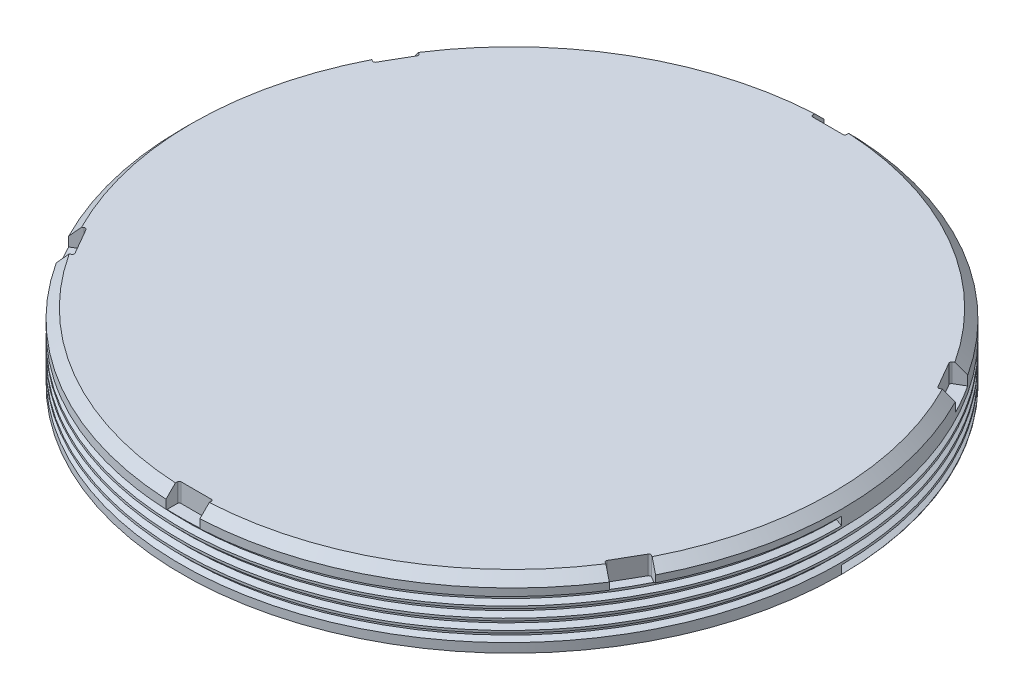
SolidWorks part; units mm, degrees
ref_plane "Front Plane" through (0, 0, 0) normal (0, 0, 1) x (1, 0, 0)
ref_plane "Top Plane" through (0, 0, 0) normal (0, 1, 0) x (1, 0, 0)
ref_plane "Right Plane" through (0, 0, 0) normal (1, 0, 0) x (0, 0, -1)
sketch "Sketch1" plane through (0, 0, 0) normal (0, 1, 0) x (1, 0, 0)
  circle A0 centre (0, 0) radius 17.5
  dimension "D1" = 35
extrude "Boss-Extrude1" add sketch "Sketch1" along normal blind 3.5
chamfer "Chamfer1" distance 0.5 angle 45 1 edges at (0, 3.5, 17.5)
sketch "Sketch3" plane through (0, 3.5, 0) normal (0, 1, 0) x (1, 0, 0)
  line L0 (14.1636, 9.2166) -> (14.7006, 9.5266)
  line L1 (14.127, 9.08) -> (14.927, 7.6944)
  line L2 (-0.8, 16.7744) -> (0.8, 16.7744)
  line L3 (0.9, 16.8744) -> (0.9, 17.4944)
  line L4 (-0.9, 16.8744) -> (-0.9, 17.4944)
  line L5 (15.0636, 7.6578) -> (15.6006, 7.9678)
  line L6 (15.0636, -7.6578) -> (15.6006, -7.9678)
  line L7 (14.927, -7.6944) -> (14.127, -9.08)
  line L8 (14.1636, -9.2166) -> (14.7006, -9.5266)
  line L9 (0.9, -16.8744) -> (0.9, -17.4944)
  line L10 (0.8, -16.7744) -> (-0.8, -16.7744)
  line L11 (-0.9, -16.8744) -> (-0.9, -17.4944)
  line L12 (-14.1636, -9.2166) -> (-14.7006, -9.5266)
  line L13 (-14.127, -9.08) -> (-14.927, -7.6944)
  line L14 (-15.0636, -7.6578) -> (-15.6006, -7.9678)
  line L15 (-15.0636, 7.6578) -> (-15.6006, 7.9678)
  line L16 (-14.927, 7.6944) -> (-14.127, 9.08)
  line L17 (-14.1636, 9.2166) -> (-14.7006, 9.5266)
  arc A0 (-14.7006, 9.5266) -> (-15.6006, 7.9678) centre (0, 0) ccw
  arc A1 (0.9, 16.8744) -> (0.8, 16.7744) centre (0.8, 16.8744) cw
  arc A2 (-0.9, 16.8744) -> (-0.8, 16.7744) centre (-0.8, 16.8744) ccw
  arc A3 (14.1636, 9.2166) -> (14.127, 9.08) centre (14.2136, 9.13) ccw
  arc A4 (15.0636, 7.6578) -> (14.927, 7.6944) centre (15.0136, 7.7444) cw
  arc A5 (15.0636, -7.6578) -> (14.927, -7.6944) centre (15.0136, -7.7444) ccw
  arc A6 (14.1636, -9.2166) -> (14.127, -9.08) centre (14.2136, -9.13) cw
  arc A7 (0.9, -16.8744) -> (0.8, -16.7744) centre (0.8, -16.8744) ccw
  arc A8 (-0.9, -16.8744) -> (-0.8, -16.7744) centre (-0.8, -16.8744) cw
  arc A9 (-14.1636, -9.2166) -> (-14.127, -9.08) centre (-14.2136, -9.13) ccw
  arc A10 (-15.0636, -7.6578) -> (-14.927, -7.6944) centre (-15.0136, -7.7444) cw
  arc A11 (-15.0636, 7.6578) -> (-14.927, 7.6944) centre (-15.0136, 7.7444) ccw
  arc A12 (-14.1636, 9.2166) -> (-14.127, 9.08) centre (-14.2136, 9.13) cw
  arc A13 (0.9, 17.4944) -> (-0.9, 17.4944) centre (0, 0) ccw
  arc A14 (15.6006, 7.9678) -> (14.7006, 9.5266) centre (0, 0) ccw
  arc A15 (-15.6006, -7.9678) -> (-14.7006, -9.5266) centre (0, 0) ccw
  arc A16 (-0.9, -17.4944) -> (0.9, -17.4944) centre (0, 0) ccw
  arc A17 (14.7006, -9.5266) -> (15.6006, -7.9678) centre (0, 0) ccw
  point P54 (0, 0)
  dimension "D1" = 6
  dimension "D2" = 0.62
extrude "Cut-Extrude1" cut sketch "Sketch3" against normal blind 1
sketch "Sketch4" plane through (0, 0, 0) normal (0, -1, 0) x (-1, 0, 0)
  circle A0 centre (0, 0) radius 15.75
  dimension "D1" = 31.5
extrude "Cut-Extrude2" cut sketch "Sketch4" against normal blind 1.5
fillet "Fillet1" radius 1 1 edges at (0, 1.5, -15.75)
thread "Thread1" pitch 0.5 method cut profile "Thread Profile2" start angle 0, offset 0, length 2.24, pitch 0.56, diameter 35
ref_plane "Plane2" through (17.5, 0, 0) normal (0, 0, 1) x (1, 0, 0)
sketch "Thread Profile2" plane through (17.5, 0, 0) normal (0, 0, 1) x (1, 0, 0)
  line L0 (0, 0) -> (0, 0.5) construction
  line L11 (0, 0) -> (0, 0.4375)
  line L12 (0, 0.4375) -> (-0.2706, 0.2812)
  line L13 (-0.2706, 0.2812) -> (-0.2706, 0.1562)
  line L15 (-0.2706, 0.1562) -> (0, 0)
  line L17 (-0.2706, 0.2187) -> (0, 0.2187) construction
  point P2 (0, 0)
  dimension "Pitch" = 0.5
  dimension "Profile_Angle" = 60
  dimension "Profile_Land" = 0.125
  dimension "Profile_Height" = 0.2706
